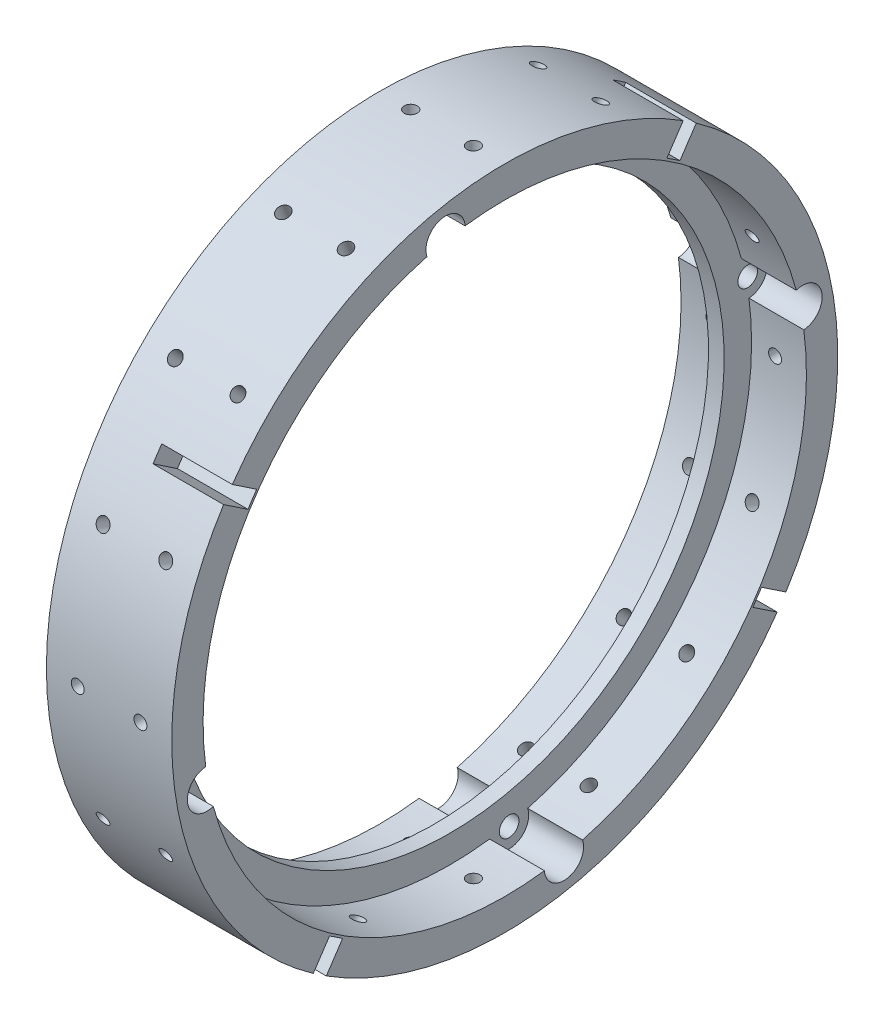
SolidWorks part; units mm, degrees
material "6061 Alloy"
ref_plane "Front Plane" through (0, 0, 0) normal (0, 0, 1) x (1, 0, 0)
ref_plane "Top Plane" through (0, 0, 0) normal (0, 1, 0) x (1, 0, 0)
ref_plane "Right Plane" through (0, 0, 0) normal (1, 0, 0) x (0, 0, -1)
sketch "Sketch2" plane through (0, 0, 0) normal (0, 0, 1) x (1, 0, 0)
  line L0 (-206.0042, 0) -> (161.3108, 0) construction
  line L1 (0, 70) -> (4, 70)
  line L2 (4, 70) -> (4, 77)
  line L3 (4, 77) -> (18, 77)
  line L4 (18, 77) -> (18, 85)
  line L5 (18, 85) -> (-14, 85)
  line L6 (-14, 85) -> (-14, 77)
  line L7 (-14, 77) -> (0, 77)
  line L8 (0, 77) -> (0, 70)
  point P5 (4, 73.5)
  dimension "D1" = 70
  dimension "D2" = 85
  dimension "D3" = 4
  dimension "D4" = 8
  dimension "D5" = 14
  dimension "D6" = 14
  dimension "D7" = 0
revolve "Revolve1" add sketch "Sketch2" angle 360 about L0
sketch "Sketch3" plane through (0, 0, 0) normal (0, 0, 1) x (1, 0, 0)
  line L0 (-20.6991, 0) -> (24.8876, 0) construction
  line L1 (-14, 85) -> (-14, -85) construction
  line L2 (18, -85) -> (18, 85) construction
  circle A0 centre (-6, 0) radius 1.65
  circle A1 centre (10, 0) radius 1.65
  dimension "D1" = 3.3
  dimension "D2" = 3.3
  dimension "D3" = 8
  dimension "D4" = 8
extrude "Cut-Extrude3" cut sketch "Sketch3" against normal blind 120
pattern_circular "CirPattern1" count 16 over 360 about axis through (-206.0042, 0, 0) along (-1, 0, 0) of "Cut-Extrude3"
sketch "Sketch4" plane through (0, 0, 0) normal (-1, 0, 0) x (0, 0, 1)
  line L0 (0, 0) -> (0, 88.2605) construction
  line L1 (0, 0) -> (-58.7208, 87.8819) construction
  line L3 (-44.7196, 63.3278) -> (-51.3865, 73.3054)
  line L4 (-41.3938, 65.55) -> (-44.7196, 63.3278)
  line L5 (-48.0606, 75.5277) -> (-51.3865, 73.3054)
  line L6 (-41.3938, 65.55) -> (-48.0606, 75.5277)
  line L7 (-1.6629, -1.1111) -> (-60.3837, 86.7708) construction
  circle A0 centre (0, 0) radius 70 construction
  point P0 (-69.9281, 3.1708)
  point P1 (0, 0)
  point P8 (1.6629, 1.1111)
  point P10 (-57.0579, 88.993)
  dimension "D4" = 77.5
  dimension "D1" = 33.75
  dimension "D2" = 2
  dimension "D3" = 2
  dimension "D5" = 12
extrude "Cut-Extrude4" cut sketch "Sketch4" against normal blind 18
pattern_circular "CirPattern2" count 4 over 360 about axis through (-206.0042, 0, 0) along (-1, 0, 0) of "Cut-Extrude4" reverse direction yes
sketch "Sketch5" plane through (18, 0, 0) normal (1, 0, 0) x (0, 0, -1)
  line L0 (-85, 0) -> (90.8502, 0) construction
  line L1 (0, 85) -> (0, -85) construction
  line L2 (0, 0) -> (-95.9688, -19.0894) construction
  arc A4 (-71.7665, 45.5475) -> (-48.8733, -69.5442) centre (0, 0) ccw construction
  arc A5 (45.5475, 71.7665) -> (-69.5442, 48.8733) centre (0, 0) ccw construction
  arc A6 (-45.5475, -71.7665) -> (69.5442, -48.8733) centre (0, 0) ccw construction
  circle A7 centre (-76.0109, -15.1195) radius 5
  dimension "D2" = 10
  dimension "D3" = 77.5
  dimension "D1" = 11.25
extrude "Cut-Extrude5" cut sketch "Sketch5" along direction (-1, 0, 0) on the side against the normal up to surface (14 mm away) contours A7 up to face at (4, 0, 77)
sketch "Sketch6" plane through (4, 0, 0) normal (1, 0, 0) x (0, 0, -1)
  circle A0 centre (-76.0109, -15.1195) radius 2.5
  dimension "D1" = 5
extrude "Cut-Extrude6" cut sketch "Sketch6" against normal blind 20
sketch "Sketch7" plane through (0, 0, 0) normal (-1, 0, 0) x (0, 0, 1)
  circle A0 centre (76.0109, -15.1195) radius 5
  dimension "D1" = 10
extrude "Cut-Extrude7" cut sketch "Sketch7" along normal blind 20
pattern_circular "CirPattern3" count 4 over 360 about axis through (-206.0042, 0, 0) along (-1, 0, 0) of "Cut-Extrude7", "Cut-Extrude6", "Cut-Extrude5" reverse direction yes
